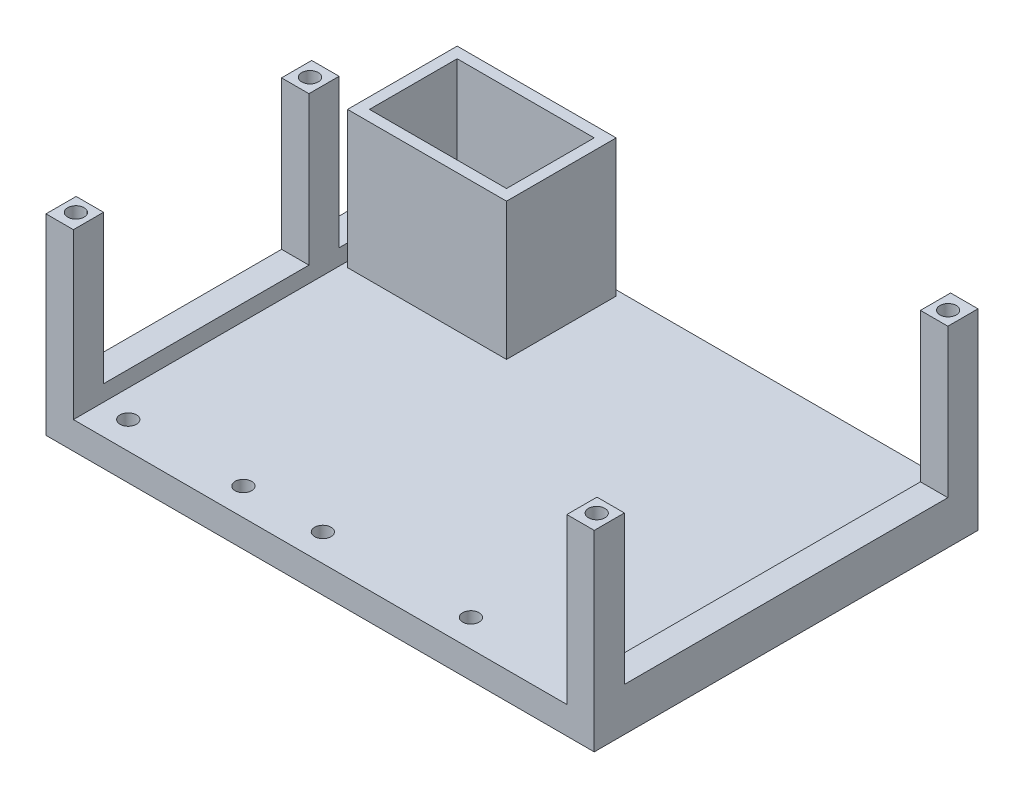
SolidWorks part; units mm, degrees
ref_plane "Front Plane" through (0, 0, 0) normal (0, 0, 1) x (1, 0, 0)
ref_plane "Top Plane" through (0, 0, 0) normal (0, 1, 0) x (1, 0, 0)
ref_plane "Right Plane" through (0, 0, 0) normal (1, 0, 0) x (0, 0, -1)
sketch "Sketch1" plane through (0, 0, 0) normal (0, 1, 0) x (1, 0, 0)
  line L1 (-45, 35) -> (45, 35)
  line L2 (-45, 35) -> (-45, -35)
  line L3 (-45, -35) -> (45, -35)
  line L4 (45, 35) -> (45, -35)
  line L5 (-45, 35) -> (45, -35) construction
  line L6 (-45, -35) -> (45, 35) construction
  point P0 (0, 0)
  dimension "D1" = 90
  dimension "D2" = 70
extrude "Boss-Extrude1" add sketch "Sketch1" along normal blind 2
sketch "Sketch2" plane through (0, 2, 0) normal (0, 1, 0) x (1, 0, 0)
  line L5 (-43, 33) -> (43, -33) construction
  line L6 (-43, -33) -> (43, 33) construction
  line L7 (-45, 35) -> (45, 35)
  line L8 (-45, 35) -> (-45, -35)
  line L9 (-45, -35) -> (45, -35)
  line L10 (45, 35) -> (45, -35)
  line L11 (-45, 35) -> (45, -35) construction
  line L12 (-45, -35) -> (45, 35) construction
  point P0 (0, 0)
  point P6 (0, 0)
extrude "Boss-Extrude2" add sketch "Sketch2" against normal blind 5
sketch "Sketch3" plane through (0, 0, 0) normal (0, -1, 0) x (1, 0, 0)
  line L0 (-45, 35) -> (45, 35) construction
  line L2 (-45, -35) -> (-45, 35) construction
  circle A0 centre (-40, 30) radius 1.5
  circle A1 centre (-19, 30) radius 1.5
  circle A6 centre (-4.5, 30) radius 1.5
  circle A7 centre (22.5, 30) radius 1.5
  dimension "D1" = 3
  dimension "D2" = 5
  dimension "D3" = 3
  dimension "D7" = 5
  dimension "D10" = 3
  dimension "D11" = 3
  dimension "D4" = 21
extrude "Cut-Extrude2" cut sketch "Sketch3" along normal blind 5 from surface starting at face at (0, 2, 0)
sketch "Sketch9" plane through (0, 2, 0) normal (0, 1, 0) x (1, 0, 0)
  line L0 (0, 0) -> (0, 6.0539) construction
  line L1 (-45, 35) -> (-50, 35)
  line L2 (-45, 35) -> (-45, -35)
  line L3 (-45, -35) -> (-50, -35)
  line L4 (-50, 35) -> (-50, -35)
  line L5 (45, -35) -> (50, -35)
  line L6 (50, 35) -> (50, -35)
  line L7 (45, 35) -> (50, 35)
  line L8 (45, 35) -> (45, -35)
  dimension "D1" = 5
extrude "Boss-Extrude6" add sketch "Sketch9" against normal blind 2
extrude "Boss-Extrude7" add sketch "Sketch9<2>" along normal blind 30
sketch "Sketch9<2>" plane through (0, 2, 0) normal (0, 1, 0) x (1, 0, 0) same geometry as "Sketch9"
sketch "Sketch10" plane through (50, 0, 0) normal (1, 0, 0) x (0, 0, -1)
  line L3 (-35, 0) -> (-35, 32) construction
  line L4 (35, 0) -> (35, 32) construction
  line L13 (-29.5, 26.8955) -> (-29.5, 7.1045)
  line L21 (-29.5, 29.0873) -> (-29.5, 26.8955)
  line L23 (-29.5, 7.1045) -> (-29.5, 4.9127)
  line L24 (29.5, 4.9127) -> (29.5, 29.0873)
  line L25 (-29.5, 4.9127) -> (29.5, 4.9127)
  line L26 (-29.5, 29.0873) -> (-29.5, 32)
  line L27 (-35, 32) -> (35, 32) construction
  line L28 (-29.5, 32) -> (29.5, 32)
  line L29 (29.5, 32) -> (29.5, 29.0873)
  point P3 (0, 0)
  dimension "D1" = 5.5
  dimension "D2" = 5.5
sketch "Sketch11" plane through (0, 2, 0) normal (0, 1, 0) x (1, 0, 0)
  line L0 (0, -14.8029) -> (0, 6.7547) construction
  line L1 (0, 0) -> (-12.8371, 0) construction
  line L2 (-50, 35) -> (-50, -35) construction
  line L3 (-50, -35) -> (-45, -35) construction
  circle A0 centre (-47.5, -32.049) radius 1.5
  circle A1 centre (-47.5, 32.049) radius 1.5
  circle A2 centre (47.5, 32.049) radius 1.5
  circle A3 centre (47.5, -32.049) radius 1.5
  dimension "D1" = 3
  dimension "D2" = 2.5
  dimension "D3" = 2.951
extrude "Cut-Extrude6" cut sketch "Sketch11" along normal through all
extrude "Cut-Extrude7" cut sketch "Sketch10" against normal blind 10 and the other way through all
sketch "Sketch12" plane through (0, 0, 0) normal (0, -1, 0) x (1, 0, 0)
  line L1 (-44, -14) -> (-15, -14)
  line L2 (-44, -14) -> (-44, -34)
  line L3 (-44, -34) -> (-15, -34)
  line L4 (-15, -14) -> (-15, -34)
  line L6 (45, -35) -> (-45, -35) construction
  line L7 (-45, -35) -> (-45, 35) construction
  dimension "D1" = 20
  dimension "D2" = 29
  dimension "D3" = 1
  dimension "D4" = 1
extrude "Boss-Extrude8" add sketch "Sketch12" against normal blind 25 from surface starting at face at (-40, 2, 31.5)
sketch "Sketch13" plane through (0, 27, 0) normal (0, 1, 0) x (-1, 0, 0)
  line L5 (44, -14) -> (15, -14) construction
  line L6 (17, -16) -> (42, -16)
  line L8 (17, -16) -> (17, -32)
  line L9 (17, -32) -> (42, -32)
  line L10 (42, -16) -> (42, -32)
  line L11 (15, -14) -> (15, -34) construction
  line L13 (44, -34) -> (44, -14) construction
  point P0 (14.5585, -23.8252)
  dimension "D1" = 2
  dimension "D2" = 2
  dimension "D3" = 16
  dimension "D4" = 2
extrude "Cut-Extrude8" cut sketch "Sketch13" against normal blind 25
sketch "Sketch14" plane through (-45, 0, 0) normal (1, 0, 0) x (0, 0, -1)
  line L0 (29.5, 4.9127) -> (-29.5, 4.9127) construction
  line L1 (35, 32) -> (13.4643, 32)
  line L2 (35, 32) -> (35, 4.9127)
  line L3 (35, 4.9127) -> (13.4643, 4.9127)
  line L4 (13.4643, 32) -> (13.4643, 4.9127)
  line L6 (-29.5, 32) -> (7.9643, 32)
  line L7 (-29.5, 32) -> (-29.5, 4.9127)
  line L8 (-29.5, 4.9127) -> (7.9643, 4.9127)
  line L9 (7.9643, 32) -> (7.9643, 4.9127)
  dimension "D1" = 5.5
extrude "Cut-Extrude9" cut sketch "Sketch14" against normal blind 25
sketch "Sketch15" plane through (0, 32, 0) normal (0, 1, 0) x (1, 0, 0)
  line L1 (-45, -35) -> (-45, 35) construction
  line L2 (-50, 13.4643) -> (-50, 7.9643) construction
  circle A0 centre (-47.5, 10.6536) radius 1.5
  dimension "D1" = 3
  dimension "D3" = 2.5
  dimension "D2" = 2.5
extrude "Cut-Extrude10" cut sketch "Sketch15" against normal blind 25
sketch "Sketch16" plane through (0, -3, 0) normal (0, -1, 0) x (1, 0, 0)
  line L1 (-50, 35) -> (-45, 35)
  line L2 (-50, 35) -> (-50, -35)
  line L3 (-50, -35) -> (-45, -35)
  line L4 (-45, 35) -> (-45, -35)
  line L5 (45, 35) -> (50, 35)
  line L6 (45, 35) -> (45, -35)
  line L7 (45, -35) -> (50, -35)
  line L8 (50, 35) -> (50, -35)
extrude "Boss-Extrude9" add sketch "Sketch16" along normal blind 3 from surface starting at face at (-47.5, 0, 0)
